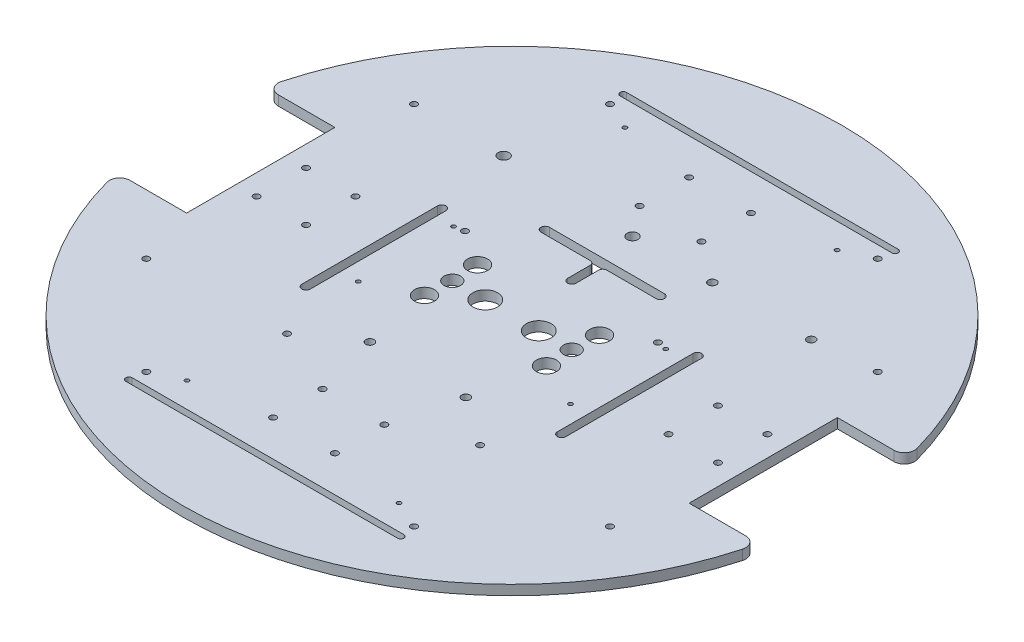
SolidWorks part; units mm, degrees
material "PMMA"
ref_plane "Front" through (0, 0, 0) normal (0, 0, 1) x (1, 0, 0)
ref_plane "Top" through (0, 0, 0) normal (0, 1, 0) x (1, 0, 0)
ref_plane "Right" through (0, 0, 0) normal (1, 0, 0) x (0, 0, -1)
sketch "草图1" plane through (0, 0, 0) normal (0, 1, 0) x (1, 0, 0)
  line L1 (160, 0) -> (80, 138.5641) construction
  line L2 (80, 138.5641) -> (-80, 138.5641) construction
  line L3 (-80, 138.5641) -> (-160, 0) construction
  line L4 (-160, 0) -> (-80, -138.5641) construction
  line L5 (-80, -138.5641) -> (80, -138.5641) construction
  line L6 (80, -138.5641) -> (160, 0) construction
  circle A0 centre (0, 0) radius 160 construction
  circle A1 centre (0, 0) radius 160
  dimension "D1" = 320
extrude "凸台-拉伸1" add sketch "草图1" along normal blind 4.8
sketch "草图2" plane through (0, 0, 0) normal (0, 1, 0) x (1, 0, 0)
  line L0 (0, 184.3432) -> (0, -209.9123) construction
  line L1 (-276.6401, 0) -> (355.4455, 0) construction
  line L2 (46.86, 49.5976) -> (46.86, -71.1191) construction
  line L3 (122, 36) -> (162, 36)
  line L4 (122, 36) -> (122, -36)
  line L5 (122, -36) -> (162, -36)
  line L6 (162, 36) -> (162, -36)
  line L7 (-107.3452, -120) -> (223.7804, -120) construction
  line L8 (-46.86, 49.5976) -> (-46.86, -71.1191) construction
  line L9 (-162, 36) -> (-162, -36)
  line L10 (-122, -36) -> (-162, -36)
  line L11 (-122, 36) -> (-122, -36)
  line L12 (-122, 36) -> (-162, 36)
  line L13 (-107.3452, 120) -> (223.7804, 120) construction
  line L14 (0, 0) -> (-188.9173, 109.0714) construction
  line L15 (67.5, 120) -> (32.5, 120) construction
  line L16 (0, 0) -> (-188.9173, -109.0714) construction
  line L17 (-67.5, -121.525) -> (-32.5, -121.525)
  line L18 (-67.5, -121.525) -> (-67.5, -118.475)
  line L19 (-67.5, -118.475) -> (-32.5, -118.475)
  line L20 (0, 0) -> (188.9173, -109.0714) construction
  line L21 (0, 0) -> (188.9173, 109.0714) construction
  line L22 (-32.5, -121.525) -> (-32.5, -118.475)
  line L23 (-50, -118.475) -> (-50, -121.525) construction
  line L24 (-67.5, -120) -> (-32.5, -120) construction
  line L25 (-17.5, -121.525) -> (17.5, -121.525)
  line L26 (-17.5, -121.525) -> (-17.5, -118.475)
  line L27 (-17.5, -118.475) -> (17.5, -118.475)
  line L28 (17.5, -121.525) -> (17.5, -118.475)
  line L29 (0, -118.475) -> (0, -121.525) construction
  line L30 (-17.5, -120) -> (17.5, -120) construction
  line L31 (67.5, -121.525) -> (32.5, -121.525)
  line L32 (67.5, -121.525) -> (67.5, -118.475)
  line L33 (67.5, -118.475) -> (32.5, -118.475)
  line L34 (32.5, -121.525) -> (32.5, -118.475)
  line L35 (50, -118.475) -> (50, -121.525) construction
  line L36 (67.5, -120) -> (32.5, -120) construction
  line L37 (50, 118.475) -> (50, 121.525) construction
  line L38 (-17.5, 120) -> (17.5, 120) construction
  line L39 (0, 118.475) -> (0, 121.525) construction
  line L40 (-67.5, 120) -> (-32.5, 120) construction
  line L41 (-50, 118.475) -> (-50, 121.525) construction
  line L42 (32.5, 121.525) -> (32.5, 118.475)
  line L43 (67.5, 118.475) -> (32.5, 118.475)
  line L44 (67.5, 121.525) -> (67.5, 118.475)
  line L45 (67.5, 121.525) -> (32.5, 121.525)
  line L46 (17.5, 121.525) -> (17.5, 118.475)
  line L47 (-17.5, 118.475) -> (17.5, 118.475)
  line L48 (-17.5, 121.525) -> (-17.5, 118.475)
  line L49 (-17.5, 121.525) -> (17.5, 121.525)
  line L50 (-32.5, 121.525) -> (-32.5, 118.475)
  line L51 (-67.5, 118.475) -> (-32.5, 118.475)
  line L52 (-67.5, 121.525) -> (-67.5, 118.475)
  line L53 (-67.5, 121.525) -> (-32.5, 121.525)
  circle A0 centre (112, 12) radius 1.55
  circle A1 centre (112, -12) radius 1.55
  circle A2 centre (88, 12) radius 1.55
  circle A3 centre (88, -12) radius 1.55
  circle A4 centre (13, 0) radius 6
  circle A5 centre (29, 0) radius 4
  circle A6 centre (46.86, 24) radius 1.55
  circle A7 centre (46.86, -62.36) radius 1.55
  circle A10 centre (-15, -101) radius 1.55
  circle A11 centre (15, -101) radius 1.55
  circle A12 centre (-15, -77) radius 1.55
  circle A13 centre (15, -77) radius 1.55
  circle A14 centre (-46.86, -62.36) radius 1.55
  circle A15 centre (-46.86, 24) radius 1.55
  circle A16 centre (-29, 0) radius 4
  circle A17 centre (-13, 0) radius 6
  circle A18 centre (-88, -12) radius 1.55
  circle A19 centre (-88, 12) radius 1.55
  circle A20 centre (-112, -12) radius 1.55
  circle A21 centre (-112, 12) radius 1.55
  circle A22 centre (15, 77) radius 1.55
  circle A23 centre (-15, 77) radius 1.55
  circle A24 centre (15, 101) radius 1.55
  circle A25 centre (-15, 101) radius 1.55
  point P27 (-50, -120)
  point P73 (0, -120)
  point P79 (50, -120)
  point P110 (50, 120)
  point P111 (0, 120)
  point P112 (-50, 120)
  dimension "D5" = 3.1
  dimension "D6" = 3.1
  dimension "D7" = 3.1
  dimension "D8" = 3.1
  dimension "D19" = 12
  dimension "D20" = 8
  dimension "D21" = 3.1
  dimension "D24" = 3.1
  dimension "D27" = 50
  dimension "D28" = 50
  dimension "D31" = 3.1
  dimension "D34" = 3.1
  dimension "D37" = 3.1
  dimension "D38" = 3.1
  dimension "D1" = 72
  dimension "D2" = 40
  dimension "D3" = 122
  dimension "D4" = 36
  dimension "D9" = 10
  dimension "D10" = 12
  dimension "D11" = 10
  dimension "D12" = 12
  dimension "D13" = 12
  dimension "D14" = 12
  dimension "D15" = 24
  dimension "D16" = 24
  dimension "D17" = 13
  dimension "D18" = 16
  dimension "D22" = 46.86
  dimension "D23" = 24
  dimension "D25" = 86.36
  dimension "D26" = 120
  dimension "D29" = 3.05
  dimension "D30" = 35
  dimension "D32" = 19
  dimension "D33" = 15
  dimension "D35" = 15
  dimension "D36" = 19
  dimension "D39" = 24
  dimension "D40" = 24
  dimension "D41" = 15
  dimension "D42" = 15
  dimension "D43" = 30
extrude "切除-拉伸1" cut sketch "草图2" against normal through all and the other way through all
sketch "草图3" plane through (0, 0, 0) normal (0, 1, 0) x (1, 0, 0)
  line L0 (0, 182.6235) -> (0, -187.0702) construction
  line L1 (-30, 46.1) -> (30, 46.1)
  line L2 (-30, 46.1) -> (-30, 42)
  line L3 (-30, 42) -> (-2.05, 42)
  line L4 (30, 46.1) -> (30, 42)
  line L5 (-150.5472, 0) -> (174.2648, 0) construction
  line L6 (-60, -40) -> (-64.1, -40)
  line L8 (-2.05, 42) -> (-2.05, 27)
  line L9 (-2.05, 27) -> (2.05, 27)
  line L10 (2.05, 42) -> (2.05, 27)
  line L11 (60, 30) -> (64.1, 30)
  line L12 (60, 30) -> (60, -40)
  line L13 (60, -40) -> (64.1, -40)
  line L14 (64.1, 30) -> (64.1, -40)
  line L19 (-60, 30) -> (-64.1, 30)
  line L20 (-64.1, 30) -> (-64.1, -40)
  line L21 (-60, 30) -> (-60, -40)
  line L22 (2.05, 42) -> (30, 42)
  point P7 (-30, 44.05)
  dimension "D1" = 4.1
  dimension "D2" = 60
  dimension "D3" = 30
  dimension "D4" = 42
  dimension "D5" = 4.1
  dimension "D6" = 15
  dimension "D7" = 2.05
  dimension "D8" = 4.1
  dimension "D9" = 70
  dimension "D10" = 30
  dimension "D11" = 60
extrude "切除-拉伸6" cut sketch "草图3" against normal through all and the other way through all
fillet "圆角3" radius 2.05 8 edges at (2.05, 2.4, -27) (-2.05, 2.4, -27) (30, 2.4, -42) (30, 2.4, -46.1) (2.05, 2.4, -42) (-2.05, 2.4, -42) (-30, 2.4, -42) (-30, 2.4, -46.1)
fillet "圆角6" radius 2.05 8 edges at (60, 2.4, 40) (64.1, 2.4, 40) (64.1, 2.4, -30) (60, 2.4, -30) (-60, 2.4, -30) (-60, 2.4, 40) (-64.1, 2.4, 40) (-64.1, 2.4, -30)
fillet "圆角7" radius 1.5 24 edges at (-67.5, 2.4, 121.525) (-67.5, 2.4, 118.475) (-32.5, 2.4, 121.525) (-32.5, 2.4, 118.475) (-17.5, 2.4, 121.525) (-17.5, 2.4, 118.475) (17.5, 2.4, 121.525) (17.5, 2.4, 118.475) (32.5, 2.4, 121.525) (32.5, 2.4, 118.475) (67.5, 2.4, 121.525) (67.5, 2.4, 118.475) (67.5, 2.4, -118.475) (67.5, 2.4, -121.525) (32.5, 2.4, -121.525) (32.5, 2.4, -118.475) (17.5, 2.4, -121.525) (17.5, 2.4, -118.475) (-17.5, 2.4, -118.475) (-17.5, 2.4, -121.525) (-32.5, 2.4, -121.525) (-32.5, 2.4, -118.475) (-67.5, 2.4, -118.475) (-67.5, 2.4, -121.525)
fillet "圆角8" radius 5 4 edges at (-155.8974, 2.4, 36) (-155.8974, 2.4, -36) (155.8974, 2.4, 36) (155.8974, 2.4, -36)
sketch "草图4" plane through (0, 4.8, 0) normal (0, 1, 0) x (1, 0, 0)
  line L0 (0, 0) -> (0, 157.1329) construction
  line L1 (140.3176, 0) -> (-140.3176, 0) construction
  line L2 (16, 121.525) -> (-16, 121.525) construction
  line L3 (15.1038, 121.525) -> (36.7767, 121.525)
  line L4 (15.1038, 121.525) -> (15.1038, 118.475)
  line L5 (15.1038, 118.475) -> (36.7767, 118.475)
  line L6 (36.7767, 121.525) -> (36.7767, 118.475)
  line L7 (34, 118.475) -> (66, 118.475) construction
  line L8 (36.7767, -121.525) -> (36.7767, -118.475)
  line L9 (15.1038, -118.475) -> (36.7767, -118.475)
  line L10 (15.1038, -121.525) -> (15.1038, -118.475)
  line L11 (15.1038, -121.525) -> (36.7767, -121.525)
  line L12 (-15.1038, -121.525) -> (-36.7767, -121.525)
  line L13 (-15.1038, -121.525) -> (-15.1038, -118.475)
  line L14 (-15.1038, -118.475) -> (-36.7767, -118.475)
  line L15 (-36.7767, -121.525) -> (-36.7767, -118.475)
  line L16 (-36.7767, 121.525) -> (-36.7767, 118.475)
  line L17 (-15.1038, 118.475) -> (-36.7767, 118.475)
  line L18 (-15.1038, 121.525) -> (-15.1038, 118.475)
  line L19 (-15.1038, 121.525) -> (-36.7767, 121.525)
  circle A0 centre (29.6142, 12.8871) radius 4.8665
  circle A1 centre (112.5833, 65) radius 1.55
  circle A2 centre (65, 112.5833) radius 1.55
  circle A3 centre (65, -112.5833) radius 1.55
  circle A4 centre (112.5833, -65) radius 1.55
  circle A5 centre (29.6142, -12.8871) radius 4.8665
  circle A6 centre (-29.6142, -12.8871) radius 4.8665
  circle A7 centre (-112.5833, -65) radius 1.55
  circle A8 centre (-65, -112.5833) radius 1.55
  circle A9 centre (-65, 112.5833) radius 1.55
  circle A10 centre (-112.5833, 65) radius 1.55
  circle A11 centre (-29.6142, 12.8871) radius 4.8665
  point P7 (0, 0)
extrude "切除-拉伸7" cut sketch "草图4" against normal blind 10
sketch "草图5" plane through (0, 4.8, 0) normal (0, 1, 0) x (1, 0, 0)
  line L0 (0, 0) -> (0, 50000) construction
  line L1 (0, 0) -> (50000, 0) construction
  circle A0 centre (-51.5075, -106.3361) radius 1
  circle A1 centre (-51.5075, -23.1386) radius 1
  circle A2 centre (-23.2909, -45.7012) radius 2
  circle A3 centre (-69.1297, 65.0872) radius 2.65
  circle A4 centre (-3.9297, 62.4372) radius 2.65
  circle A5 centre (34.837, 62.4372) radius 2
  circle A6 centre (82.837, 62.4372) radius 2
  circle A7 centre (51.5075, -106.3361) radius 1
  circle A8 centre (51.5075, -23.1386) radius 1
  circle A11 centre (23.2909, -45.7012) radius 2
extrude "切除-拉伸8" cut sketch "草图5" against normal blind 10
sketch "草图6" plane through (0, 4.8, 0) normal (0, 1, 0) x (1, 0, 0)
  line L0 (0, 0) -> (-217.5746, 0) construction
  line L1 (0, 0) -> (0, 50000) construction
  circle A5 centre (-51.5075, -23.1386) radius 1
  circle A6 centre (51.5075, -23.1386) radius 1
  circle A7 centre (51.5075, -106.3361) radius 1
  circle A8 centre (-51.5075, -106.3361) radius 1
  circle A9 centre (-51.5075, 106.3361) radius 1
  circle A10 centre (51.5075, 106.3361) radius 1
  circle A11 centre (51.5075, 23.1386) radius 1
  circle A12 centre (-51.5075, 23.1386) radius 1
extrude "切除-拉伸10" cut sketch "草图6" against normal blind 5
